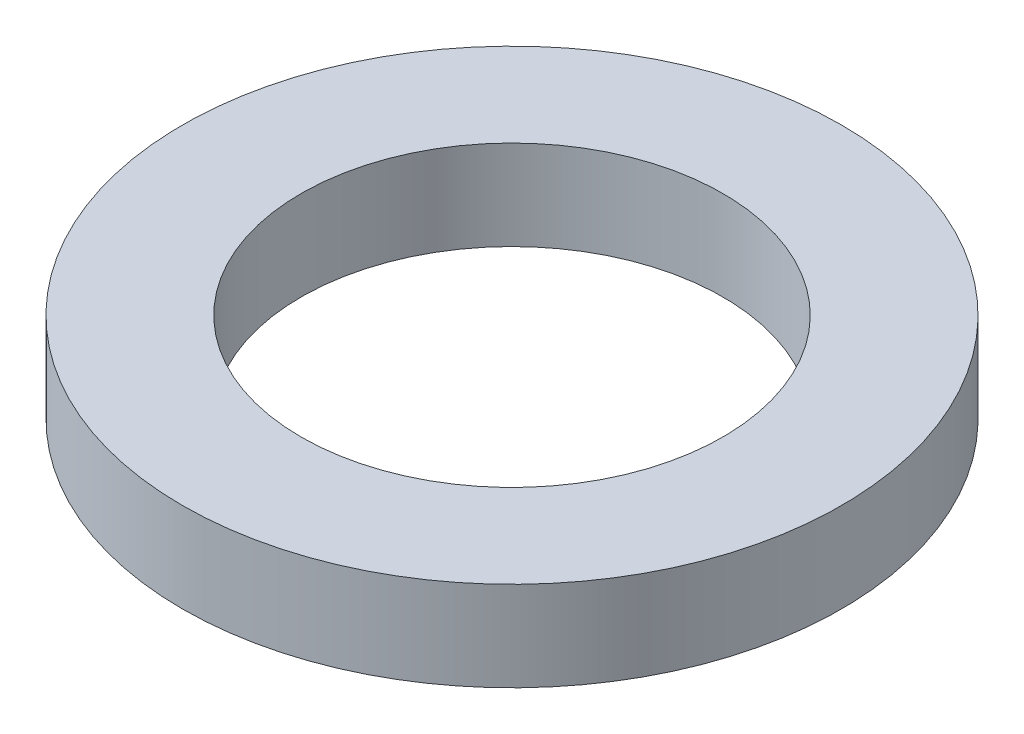
SolidWorks part; units mm, degrees
ref_plane "Front Plane" through (0, 0, 0) normal (0, 0, 1) x (1, 0, 0)
ref_plane "Top Plane" through (0, 0, 0) normal (0, 1, 0) x (1, 0, 0)
ref_plane "Right Plane" through (0, 0, 0) normal (1, 0, 0) x (0, 0, -1)
sketch "Sketch1" plane through (0, 0, 0) normal (0, 1, 0) x (1, 0, 0)
  circle A0 centre (0, 0) radius 62.5
  dimension "FLANGE_OD" = 125
extrude "Boss-Extrude1" add sketch "Sketch1" along normal blind 17
sketch "Sketch2" plane through (0, 0, 0) normal (0, 1, 0) x (1, 0, 0)
  circle A0 centre (0, 0) radius 40
  dimension "BORE_D" = 80
extrude "Cut-Extrude1" cut sketch "Sketch2" along normal through all
sketch "Sketch3" plane through (0, 17, 0) normal (0, 1, 0) x (1, 0, 0)
  circle A0 centre (0, 0) radius 26.7959 construction
  circle A1 centre (-26.7959, 0) radius 3.1828
  dimension "BOLT_D" = 6.3657
  dimension "BOLT_PCD" = 53.5919
extrude "Cut-Extrude2" cut sketch "Sketch3" against normal blind 10.2492 rebuild error yes
pattern_circular "CirPattern1" count 5 over 360 rebuild error yes
